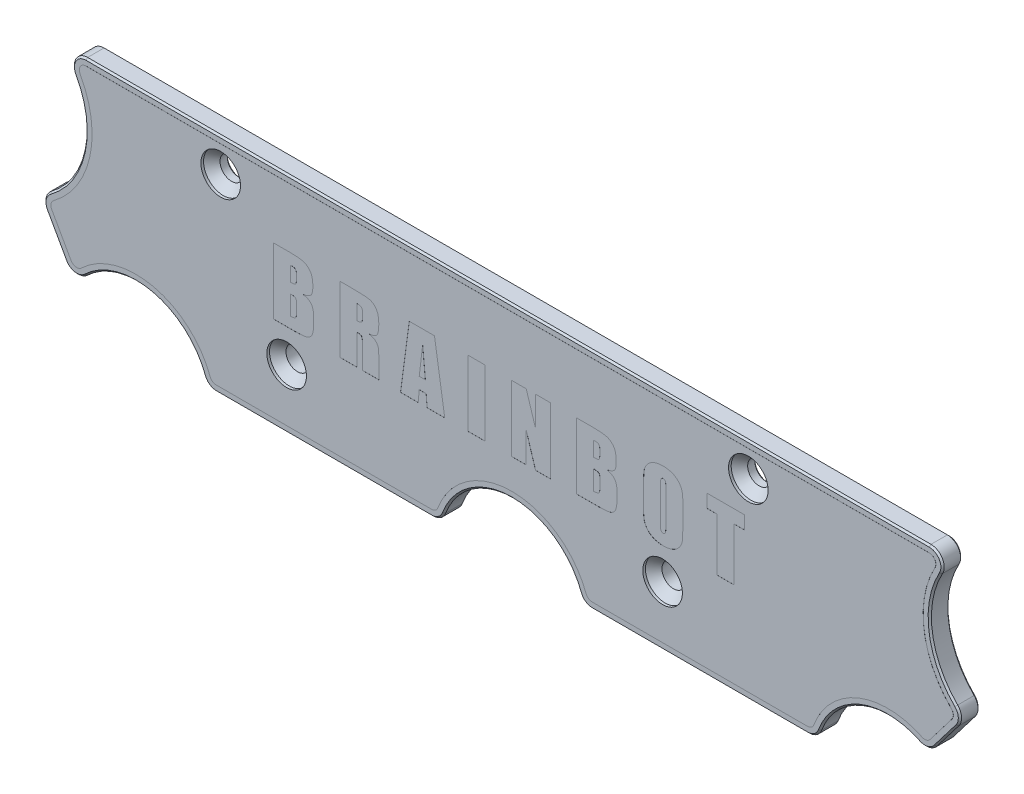
SolidWorks part; units mm, degrees
ref_plane "Front Plane" through (0, 0, 0) normal (0, 0, 1) x (1, 0, 0)
ref_plane "Top Plane" through (0, 0, 0) normal (0, 1, 0) x (1, 0, 0)
ref_plane "Right Plane" through (0, 0, 0) normal (1, 0, 0) x (0, 0, -1)
sketch "Sketch1" plane through (0, 0, 0) normal (0, 0, 1) x (1, 0, 0)
  line L1 (22.6863, -24.5) -> (-170.6863, -24.5) construction
  line L2 (0, 9.5) -> (-155, 9.5)
  line L3 (0, 9.5) -> (-155, 9.5)
  line L4 (22.6863, -24.5) -> (-170.6863, -24.5)
  line L5 (-168, -15.5) -> (-138, -35.5) construction
  line L6 (-175.3726, -15.5) -> (-159.296, -15.5) construction
  line L7 (-168, -15.5) -> (-133.8458, -27.0539) construction
  line L9 (-155, 0) -> (-141.2905, -24.5)
  line L10 (-77.5, 9.5) -> (-77.5, -24.5) construction
  line L11 (0, 0) -> (-18.7354, -24.5)
  line L13 (-165.9083, -6.104) -> (-146.7267, -40.3832) construction
  line L14 (-16.0564, -41.5745) -> (9.9295, -7.5932) construction
  circle A0 centre (-121, 4.5) radius 1.75 construction
  circle A1 centre (-121, 4.5) radius 1.75
  circle A2 centre (-41, 4.5) radius 1.75 construction
  circle A3 centre (-41, 4.5) radius 1.75
  circle A4 centre (-111, -15.5) radius 1.75
  circle A5 centre (-54, -15.5) radius 1.75
  circle A8 centre (-155, 0) radius 13.5
  circle A9 centre (-155, 0) radius 13.5
  circle A11 centre (0, 0) radius 13.5
  circle A12 centre (0, 0) radius 13.5
  circle A14 centre (-133.8458, -27.0539) radius 10 construction
  circle A15 centre (-138, -35.5) radius 10 construction
  circle A16 centre (-133.8458, -27.0539) radius 11
  circle A17 centre (-76.8458, -27.0539) radius 11
  circle A18 centre (-19.8458, -27.0539) radius 11
  point P41 (-144.5453, -24.5)
  point P47 (-168, -15.5)
  point P48 (-54, -15.5)
  dimension "D4" = 15
  dimension "D7" = 57
  dimension "D1" = 1
  dimension "D2" = 1
  dimension "D3" = 3
  dimension "D5" = 1
  dimension "D6" = 3
extrude "Boss-Extrude1" add sketch "Sketch1" along normal blind 3 contours A18 L4 A12 L3 A9 L9 A16 A17 A1 A3 A4 A5 region at (-77.8364, -6.307, 0)
sketch "Sketch2" plane through (0, 0, 0) normal (0, 0, -1) x (-1, 0, 0)
  circle A0 centre (111, -15.5) radius 1.75 construction
  circle A1 centre (54, -15.5) radius 1.75 construction
  circle A2 centre (111, -15.5) radius 1.75
  circle A3 centre (54, -15.5) radius 1.75
  circle A4 centre (54, -15.5) radius 2.75
  circle A5 centre (111, -15.5) radius 2.75
  dimension "D1" = 1
extrude "Boss-Extrude2" add sketch "Sketch2" along normal up to surface (12.55 mm away)
hole_wizard "CSK for M3 Flat Head Machine Screw1" positions "Sketch3" profile "Sketch4" countersink size "M3" standard "ANSI Metric" end condition through all
sketch "Sketch3" plane through (0, 0, 3) normal (0, 0, 1) x (1, 0, 0)
  point P0 (-121, 4.5)
  point P3 (-41, 4.5)
  point P6 (-54, -15.5)
  point P9 (-111, -15.5)
sketch "Sketch4" plane through (-121, 4.5, 3) normal (1, 0, 0) x (0, -1, 0)
  line L0 (0, 0) -> (0, 15.55)
  line L1 (0, 15.55) -> (1.75, 15.55)
  line L2 (1.75, 15.55) -> (1.75, 1.65)
  line L3 (1.75, 1.65) -> (3, 0.4)
  line L4 (3, 0.4) -> (3, 0)
  line L6 (3, 0) -> (0, 0)
  line L7 (-1.75, 1.65) -> (-3, 0.4) construction
  line L11 (0, -6.35) -> (0, 107.95) construction
  dimension "Thru Hole Dia." = 3.5
  dimension "Thru Hole Depth" = 15.55
  dimension "C'Sink Dia." = 6
  dimension "C'Sink Angle" = 90
  dimension "Head Clearance" = 0.4
fillet "Fillet1" radius 2 12 edges at (-9.5917, 9.5, 1.5) (-30.5453, -24.5, 1.5) (-66.1464, -24.5, 1.5) (-87.5453, -24.5, 1.5) (-123.1464, -24.5, 1.5) (-145.4083, 9.5, 1.5) (-148.4077, -11.781, 1.5) (-8.2006, -10.7238, 1.5) (-13.7079, -17.9256, 1.5) (-143.1473, -21.1817, 1.5) (-56.75, -15.5, 0) (-113.75, -15.5, 0)
sketch "Sketch5" plane through (0, 0, 3) normal (0, 0, 1) x (1, 0, 0)
  line L0 (-146.5147, -10.5) -> (-8.4853, -10.5) construction
  line L1 (-13.5647, 9.5) -> (-141.4353, 9.5) construction
  arc A0 (-11.8144, 6.5323) -> (-9.5158, -9.576) centre (0, 0) ccw construction
  arc A1 (-146.9427, -10.8319) -> (-143.1856, 6.5323) centre (-155, 0) ccw construction
  text T0 "BRAINBOT" font "Impact" height 10
  point P5 (-143.6417, -7.2965)
  dimension "D1" = 20
extrude "Cut-Extrude1" cut sketch "Sketch5" against normal blind 0.01
sketch "Sketch7" plane through (0, 0, 3) normal (0, 0, 1) x (1, 0, 0)
  line L0 (-147.4943, -13.4132) -> (-144.5736, -18.6329) construction
  line L1 (-89.0221, -24.5) -> (-121.6696, -24.5) construction
  line L2 (-32.0221, -24.5) -> (-64.6696, -24.5) construction
  line L3 (-9.3368, -12.2096) -> (-12.6489, -16.5408) construction
  line L4 (-13.5647, 9.5) -> (-141.4353, 9.5) construction
  line L5 (-147.4943, -13.4132) -> (-144.5736, -18.6329)
  line L6 (-89.0221, -24.5) -> (-121.6696, -24.5)
  line L7 (-32.0221, -24.5) -> (-64.6696, -24.5)
  line L8 (-9.3368, -12.2096) -> (-12.6489, -16.5408)
  line L9 (-13.5647, 9.5) -> (-141.4353, 9.5)
  line L10 (-13.5647, 8.5) -> (-141.4353, 8.5)
  line L11 (-146.6217, -12.9249) -> (-143.7009, -18.1446)
  line L12 (-89.0221, -23.5) -> (-121.6696, -23.5)
  line L13 (-32.0221, -23.5) -> (-64.6696, -23.5)
  line L14 (-10.1312, -11.6021) -> (-13.4433, -15.9333)
  arc A0 (-141.4353, 9.5) -> (-143.1856, 6.5323) centre (-141.4353, 7.5) ccw construction
  arc A1 (-146.9427, -10.8319) -> (-143.1856, 6.5323) centre (-155, 0) ccw construction
  arc A2 (-146.9427, -10.8319) -> (-147.4943, -13.4132) centre (-145.749, -12.4366) ccw construction
  arc A3 (-144.5736, -18.6329) -> (-141.4463, -19.1021) centre (-142.8282, -17.6563) ccw construction
  arc A4 (-123.5428, -23.2006) -> (-141.4463, -19.1021) centre (-133.8458, -27.0539) ccw construction
  arc A5 (-123.5428, -23.2006) -> (-121.6696, -24.5) centre (-121.6696, -22.5) ccw construction
  arc A6 (-89.0221, -24.5) -> (-87.1488, -23.2006) centre (-89.0221, -22.5) ccw construction
  arc A7 (-66.5428, -23.2006) -> (-87.1488, -23.2006) centre (-76.8458, -27.0539) ccw construction
  arc A8 (-66.5428, -23.2006) -> (-64.6696, -24.5) centre (-64.6696, -22.5) ccw construction
  arc A9 (-32.0221, -24.5) -> (-30.1488, -23.2006) centre (-32.0221, -22.5) ccw construction
  arc A10 (-15.1004, -17.1302) -> (-30.1488, -23.2006) centre (-19.8458, -27.0539) ccw construction
  arc A11 (-15.1004, -17.1302) -> (-12.6489, -16.5408) centre (-14.2376, -15.3259) ccw construction
  arc A12 (-9.3368, -12.2096) -> (-9.5158, -9.576) centre (-10.9255, -10.9947) ccw construction
  arc A13 (-11.8144, 6.5323) -> (-9.5158, -9.576) centre (0, 0) ccw construction
  arc A14 (-11.8144, 6.5323) -> (-13.5647, 9.5) centre (-13.5647, 7.5) ccw construction
  arc A15 (-141.4353, 9.5) -> (-143.1856, 6.5323) centre (-141.4353, 7.5) ccw
  arc A16 (-146.9427, -10.8319) -> (-143.1856, 6.5323) centre (-155, 0) ccw
  arc A17 (-146.9427, -10.8319) -> (-147.4943, -13.4132) centre (-145.749, -12.4366) ccw
  arc A18 (-144.5736, -18.6329) -> (-141.4463, -19.1021) centre (-142.8282, -17.6563) ccw
  arc A19 (-123.5428, -23.2006) -> (-141.4463, -19.1021) centre (-133.8458, -27.0539) ccw
  arc A20 (-123.5428, -23.2006) -> (-121.6696, -24.5) centre (-121.6696, -22.5) ccw
  arc A21 (-89.0221, -24.5) -> (-87.1488, -23.2006) centre (-89.0221, -22.5) ccw
  arc A22 (-66.5428, -23.2006) -> (-87.1488, -23.2006) centre (-76.8458, -27.0539) ccw
  arc A23 (-66.5428, -23.2006) -> (-64.6696, -24.5) centre (-64.6696, -22.5) ccw
  arc A24 (-32.0221, -24.5) -> (-30.1488, -23.2006) centre (-32.0221, -22.5) ccw
  arc A25 (-15.1004, -17.1302) -> (-30.1488, -23.2006) centre (-19.8458, -27.0539) ccw
  arc A26 (-15.1004, -17.1302) -> (-12.6489, -16.5408) centre (-14.2376, -15.3259) ccw
  arc A27 (-9.3368, -12.2096) -> (-9.5158, -9.576) centre (-10.9255, -10.9947) ccw
  arc A28 (-11.8144, 6.5323) -> (-9.5158, -9.576) centre (0, 0) ccw
  arc A29 (-11.8144, 6.5323) -> (-13.5647, 9.5) centre (-13.5647, 7.5) ccw
  arc A30 (-141.4353, 8.5) -> (-142.3105, 7.0161) centre (-141.4353, 7.5) ccw
  arc A31 (-146.3458, -11.6342) -> (-142.3105, 7.0161) centre (-155, 0) ccw
  arc A32 (-146.3458, -11.6342) -> (-146.6217, -12.9249) centre (-145.749, -12.4366) ccw
  arc A33 (-143.7009, -18.1446) -> (-142.1373, -18.3792) centre (-142.8282, -17.6563) ccw
  arc A34 (-122.6062, -22.8503) -> (-142.1373, -18.3792) centre (-133.8458, -27.0539) ccw
  arc A35 (-122.6062, -22.8503) -> (-121.6696, -23.5) centre (-121.6696, -22.5) ccw
  arc A36 (-89.0221, -23.5) -> (-88.0855, -22.8503) centre (-89.0221, -22.5) ccw
  arc A37 (-65.6062, -22.8503) -> (-88.0855, -22.8503) centre (-76.8458, -27.0539) ccw
  arc A38 (-65.6062, -22.8503) -> (-64.6696, -23.5) centre (-64.6696, -22.5) ccw
  arc A39 (-32.0221, -23.5) -> (-31.0855, -22.8503) centre (-32.0221, -22.5) ccw
  arc A40 (-14.669, -16.228) -> (-31.0855, -22.8503) centre (-19.8458, -27.0539) ccw
  arc A41 (-14.669, -16.228) -> (-13.4433, -15.9333) centre (-14.2376, -15.3259) ccw
  arc A42 (-10.1312, -11.6021) -> (-10.2206, -10.2854) centre (-10.9255, -10.9947) ccw
  arc A43 (-12.6895, 7.0161) -> (-10.2206, -10.2854) centre (0, 0) ccw
  arc A44 (-12.6895, 7.0161) -> (-13.5647, 8.5) centre (-13.5647, 7.5) ccw
  dimension "D1" = 1
extrude "Cut-Extrude2" cut sketch "Sketch7" against normal blind 0.01
chamfer "Chamfer1" distance 0.25 angle 45 46 edges at (-51.25, -15.5, -12.55) (-52.25, -15.5, -12.55) (-108.25, -15.5, -12.55) (-109.25, -15.5, -12.55) (-119.25, 4.5, 0) (-39.25, 4.5, 0) (-76.8458, -16.0539, 0) (-65.8095, -24.1434, 0) (-87.8822, -24.1434, 0) (-48.3458, -24.5, 0) (-105.3458, -24.5, 0) (-30.8822, -24.1434, 0) (-122.8095, -24.1434, 0) (-23.961, -16.8527, 0) (-131.3912, -16.3313, 0) (-13.7701, -17.2705, 0) (-143.125, -19.6341, 0) (-10.9928, -14.3752, 0) (-146.034, -16.0231, 0) (-8.9301, -10.8591, 0) (-147.7048, -12.0186, 0) (-13.3646, -1.9071, 0) (-141.8053, -2.8549, 0) (-11.8419, 8.516, 0) (-143.1581, 8.516, 0) (-77.5, 9.5, 0) (-76.8458, -16.0539, 2.99) (-65.8095, -24.1434, 2.99) (-87.8822, -24.1434, 2.99) (-48.3458, -24.5, 2.99) (-105.3458, -24.5, 2.99) (-30.8822, -24.1434, 2.99) (-122.8095, -24.1434, 2.99) (-23.961, -16.8527, 2.99) (-131.3912, -16.3313, 2.99) (-13.7701, -17.2705, 2.99) (-143.125, -19.6341, 2.99) (-10.9928, -14.3752, 2.99) (-146.034, -16.0231, 2.99) (-8.9301, -10.8591, 2.99) (-147.7048, -12.0186, 2.99) (-13.3646, -1.9071, 2.99) (-141.8053, -2.8549, 2.99) (-11.8419, 8.516, 2.99) (-143.1581, 8.516, 2.99) (-77.5, 9.5, 2.99)
